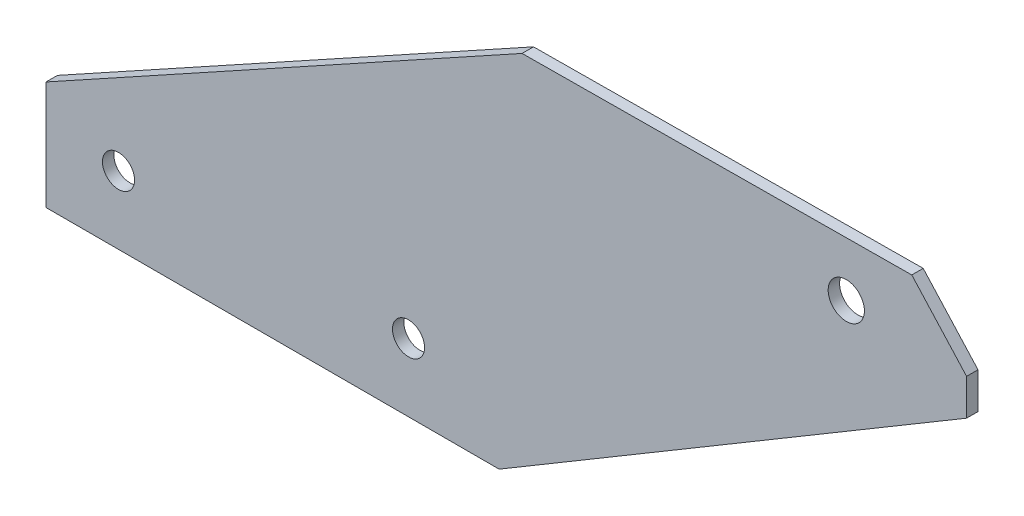
SolidWorks part; units mm, degrees
ref_plane "Front Plane" through (0, 0, 0) normal (0, 0, 1) x (1, 0, 0)
ref_plane "Top Plane" through (0, 0, 0) normal (0, 1, 0) x (1, 0, 0)
ref_plane "Right Plane" through (0, 0, 0) normal (1, 0, 0) x (0, 0, -1)
sketch "Sketch1" plane through (0, 0, 0) normal (0, 0, 1) x (1, 0, 0)
  line L0 (0, 0) -> (0, 15.24)
  line L1 (0, 15.24) -> (66.7136, 52.0603)
  line L2 (0, 0) -> (63.5, 0)
  line L3 (55, 0) -> (-55, 0) construction
  line L4 (66.7136, 52.0603) -> (121.3236, 52.4827)
  line L5 (121.3236, 52.4827) -> (129.0016, 44.0156)
  line L6 (129.0016, 44.0156) -> (129.0016, 38.9356)
  line L7 (129.0016, 38.9356) -> (63.5, 0)
  circle A2 centre (10.16, 9.525) radius 2.2479
  circle A3 centre (50.8, 9.525) radius 2.2479
  circle A5 centre (112.1444, 44.7915) radius 2.54
  dimension "D9" = 5.08
  dimension "D11" = 4.4958
  dimension "D12" = 9.525
  dimension "D13" = 10.16
  dimension "D14" = 4.4958
  dimension "D15" = 40.64
  dimension "D16" = 9.525
  dimension "D2" = 63.5
  dimension "D3" = 15.24
  dimension "D4" = 76.2
  dimension "D5" = 76.2
  dimension "D6" = 54.61
  dimension "D7" = 11.43
  dimension "D8" = 5.08
  dimension "D10" = 7.62
extrude "Boss-Extrude1" add sketch "Sketch1" against normal blind 1.6002
